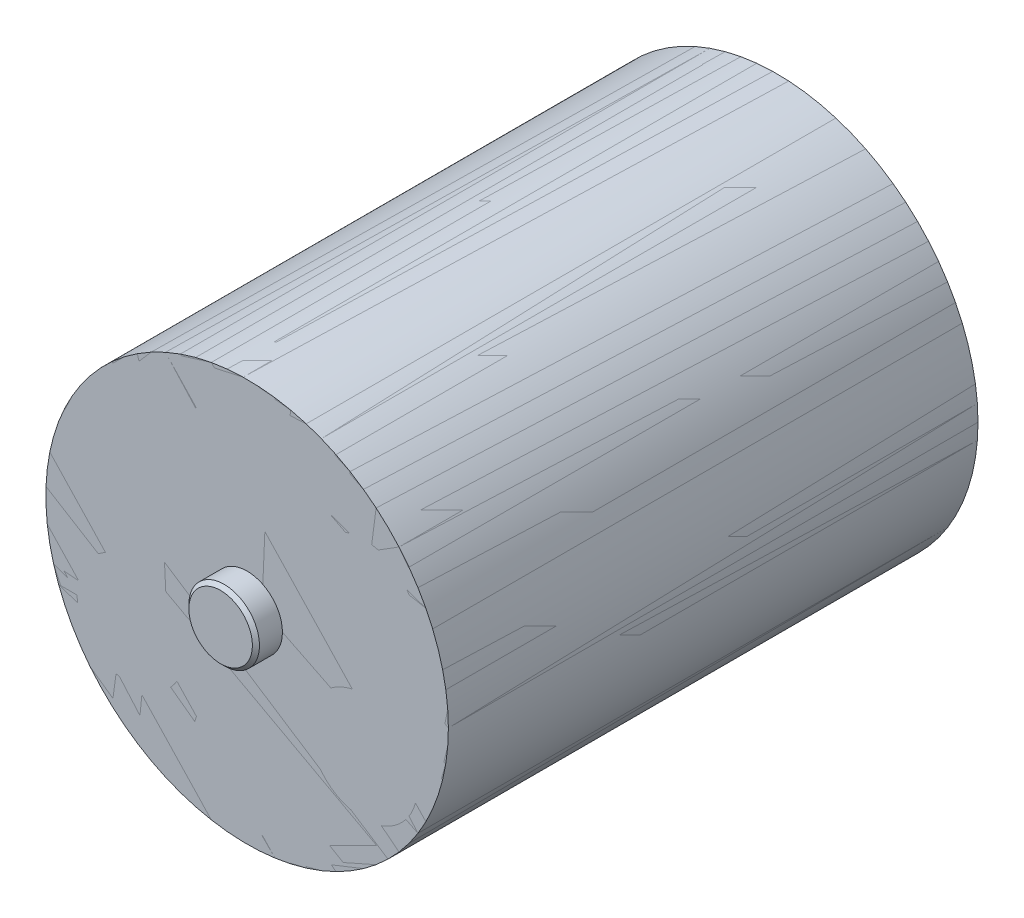
SolidWorks part; units mm, degrees
other "COLL.CYLINDER-Boss-Extrude3"
ref_plane "Piano frontale" through (0, 0, 0) normal (0, 0, 1) x (1, 0, 0)
ref_plane "Piano superiore" through (0, 0, 0) normal (0, 1, 0) x (1, 0, 0)
ref_plane "Piano destro" through (0, 0, 0) normal (1, 0, 0) x (0, 0, -1)
sketch "Sketch1" plane through (0, 0, 0) normal (0, 0, 1) x (1, 0, 0)
  line L0 (271.212, 527.9944) -> (271.212, 413.9944) construction
  circle A0 centre (271.212, 413.9944) radius 114
  dimension "D1" = 228
extrude "Boss-Extrude1" add sketch "Sketch1" against normal mid plane 300
sketch3d "3DSketch1"
  line L0 (271.212, 413.9944, 150) -> (271.212, 413.9944, -150)
  line L1 (271.212, 413.9944, -150) -> (271.212, 413.9944, 150) construction
  line L2 (271.212, 413.9944, 150) -> (271.212, 413.9944, 0)
  line L3 (271.212, 413.9944, 0) -> (271.212, 465.8799, 0)
ref_axis "Axis1" through (271.212, 413.9944, 150) along (0, 0, -1)
sketch "Sketch2" plane through (0, 0, 150) normal (0, 0, 1) x (1, 0, 0)
  line L0 (271.212, 413.9944) -> (271.212, 490.0656) construction
  circle A0 centre (271.212, 490.0656) radius 30.584
extrude "Cut-Extrude1" cut sketch "Sketch2" against normal blind 5
pattern_circular "CirPattern1" count 6 over 360 of "Cut-Extrude1"
mirror "Mirror1" about plane through (0, 0, 0) normal (0, 0, 1) of "CirPattern1"
sketch "Sketch3" plane through (0, 0, 150) normal (0, 0, 1) x (1, 0, 0)
  circle A0 centre (271.212, 413.9944) radius 20
extrude "Boss-Extrude2" add sketch "Sketch3" along normal blind 15
chamfer "Chamfer1" distance 2 angle 45 1 edges at (291.212, 413.9944, 165)
mirror "Mirror4" about plane through (0, 0, 0) normal (0, 0, 1) of "Boss-Extrude2"
sketch "Sketch4" plane through (0, 0, 150) normal (0, 0, 1) x (1, 0, 0)
  circle A0 centre (271.212, 413.9944) radius 114 construction
  circle A1 centre (271.212, 413.9944) radius 114
extrude "Boss-Extrude3" add sketch "Sketch4" against normal up to surface (300 mm away) separate body up to face at (291.212, 413.9944, -150)
